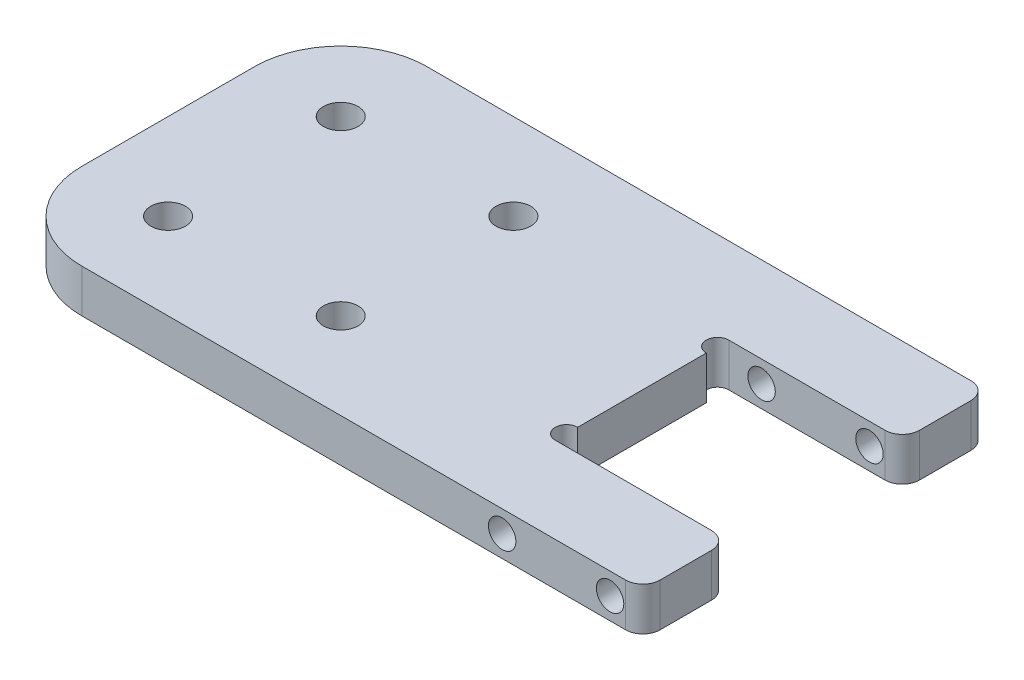
SolidWorks part; units mm, degrees
material "6061-T6 (SS)"
ref_plane "Front Plane" through (0, 0, 0) normal (0, 0, 1) x (1, 0, 0)
ref_plane "Top Plane" through (0, 0, 0) normal (0, 1, 0) x (1, 0, 0)
ref_plane "Right Plane" through (0, 0, 0) normal (1, 0, 0) x (0, 0, -1)
sketch "Sketch1" plane through (0, 0, 0) normal (0, 1, 0) x (1, 0, 0)
  line L0 (34.925, 25.4) -> (60.325, 25.4)
  line L1 (-34.925, -25.4) -> (34.925, -25.4)
  line L2 (-34.925, -25.4) -> (-34.925, 25.4)
  line L3 (-34.925, 25.4) -> (34.925, 25.4)
  line L5 (-34.925, -25.4) -> (34.925, 25.4) construction
  line L6 (-34.925, 25.4) -> (34.925, -25.4) construction
  line L7 (60.325, 25.4) -> (60.325, -25.4)
  line L8 (60.325, -25.4) -> (34.925, -25.4)
  point P0 (0, 0)
  dimension "D1" = 69.85
  dimension "D2" = 50.8
  dimension "D3" = 25.4
extrude "Boss-Extrude1" add sketch "Sketch1" along normal blind 6.35
sketch "Sketch2" plane through (0, 6.35, 0) normal (0, 1, 0) x (1, 0, 0)
  line L4 (60.325, 25.4) -> (-34.925, 25.4) construction
  line L5 (-34.925, -25.4) -> (60.325, -25.4) construction
  line L7 (15.875, 25.4) -> (15.875, -25.4) construction
  line L8 (-34.925, 25.4) -> (-34.925, -25.4) construction
  dimension "D1" = 50.8
hole_wizard "#10 Clearance Hole1" positions "Sketch3" profile "Sketch4" hole size "#10" standard "ANSI Inch" end condition through all
sketch "Sketch3" plane through (0, 6.35, 0) normal (0, 1, 0) x (1, 0, 0)
  line L4 (-22.225, 25.4) -> (-22.225, -25.4) construction
  line L5 (60.325, 25.4) -> (-34.925, 25.4) construction
  line L6 (-34.925, -25.4) -> (60.325, -25.4) construction
  line L8 (3.175, 25.4) -> (3.175, -25.4) construction
  line L9 (-34.925, 25.4) -> (-34.925, -25.4) construction
  line L11 (-34.925, 12.7) -> (15.875, 12.7) construction
  line L13 (-34.925, -12.7) -> (15.875, -12.7) construction
  point P0 (-22.225, 12.7)
  point P2 (3.175, 12.7)
  point P4 (3.175, -12.7)
  point P6 (-22.225, -12.7)
  dimension "D1" = 12.7
  dimension "D2" = 38.1
  dimension "D3" = 12.7
  dimension "D4" = 12.7
  dimension "D5" = 50.8
  dimension "D6" = 50.8
sketch "Sketch4" plane through (-22.225, 6.35, -12.7) normal (1, 0, 0) x (0, 0, 1)
  line L0 (0, 0) -> (0, 6.35)
  line L1 (0, 6.35) -> (2.5527, 6.35)
  line L2 (2.5527, 6.35) -> (2.5527, 0)
  line L5 (2.5527, 0) -> (0, 0)
  line L11 (0, -6.35) -> (0, 107.95) construction
  dimension "Thru Hole Dia." = 5.1054
  dimension "Thru Hole Depth" = 6.35
sketch "Sketch5" plane through (0, 6.35, 0) normal (0, 1, 0) x (1, 0, 0)
  line L1 (60.325, -25.4) -> (60.325, 25.4) construction
  line L2 (34.798, -12.7635) -> (60.325, -12.7635)
  line L4 (34.798, -12.7635) -> (34.798, 12.7635)
  line L5 (34.798, 12.7635) -> (60.325, 12.7635)
  line L6 (60.325, -12.7635) -> (60.325, 12.7635)
  line L7 (34.798, -12.7635) -> (60.325, 12.7635) construction
  line L8 (34.798, 12.7635) -> (60.325, -12.7635) construction
  line L13 (60.325, 12.7635) -> (60.325, 25.4) construction
  line L14 (60.325, -12.7635) -> (60.325, -25.4) construction
  dimension "D3" = 25.527
extrude "Cut-Extrude1" cut sketch "Sketch5" against normal through all
sketch "Sketch6" plane through (0, 6.35, 0) normal (0, 1, 0) x (1, 0, 0)
  line L0 (34.798, 12.7635) -> (34.798, -12.7635) construction
  line L1 (34.798, 9.4615) -> (34.798, 12.7635)
  line L2 (34.798, 0) -> (41.7316, 0) construction
  line L3 (34.798, -9.4615) -> (34.798, -12.7635)
  arc A0 (34.798, 12.7635) -> (34.798, 9.4615) centre (34.798, 11.1125) ccw
  arc A1 (34.798, -12.7635) -> (34.798, -9.4615) centre (34.798, -11.1125) cw
  dimension "D1" = 3.302
extrude "Cut-Extrude2" cut sketch "Sketch6" against normal through all
fillet "Fillet1" radius 2.54 4 edges at (60.325, 3.175, 12.7635) (60.325, 3.175, -12.7635) (60.325, 3.175, -25.4) (60.325, 3.175, 25.4)
fillet "Fillet2" radius 12.7 2 edges at (-34.925, 3.175, -25.4) (-34.925, 3.175, 25.4)
sketch "Sketch10" plane through (0, 0, 25.4) normal (0, 0, 1) x (1, 0, 0)
  line L2 (34.798, 6.35) -> (39.624, 3.175) construction
  line L3 (-22.225, 6.35) -> (57.785, 6.35) construction
  line L8 (55.499, 3.175) -> (60.325, 0) construction
  point P0 (55.499, 3.175)
  point P2 (39.624, 3.175)
  point P23 (54.489, 2.8137)
  point P25 (41.3485, 3.153)
  point P26 (0, 0)
  point P28 (0, 0)
  dimension "D1" = 15.875
hole_wizard "#10-32 Tapped Hole1" positions "Sketch10" profile "Sketch9" tap size "#10-32" standard "ANSI Inch" end condition through all
sketch "Sketch9" plane through (55.499, 3.175, 25.4) normal (1, 0, 0) x (0, -1, 0)
  line L0 (0, 0) -> (0, 50.8)
  line L1 (0, 50.8) -> (2.0193, 50.8)
  line L2 (2.0193, 50.8) -> (2.0193, 0)
  line L5 (2.0193, 0) -> (0, 0)
  line L11 (0, -6.35) -> (0, 107.95) construction
  dimension "Thru Tap Drill Dia." = 4.0386
  dimension "Thru Tap Drill Depth" = 50.8
cosmetic thread "Hole Thread1" parameters "D2"=4.826
cosmetic thread "Hole Thread2" parameters "D2"=4.826
